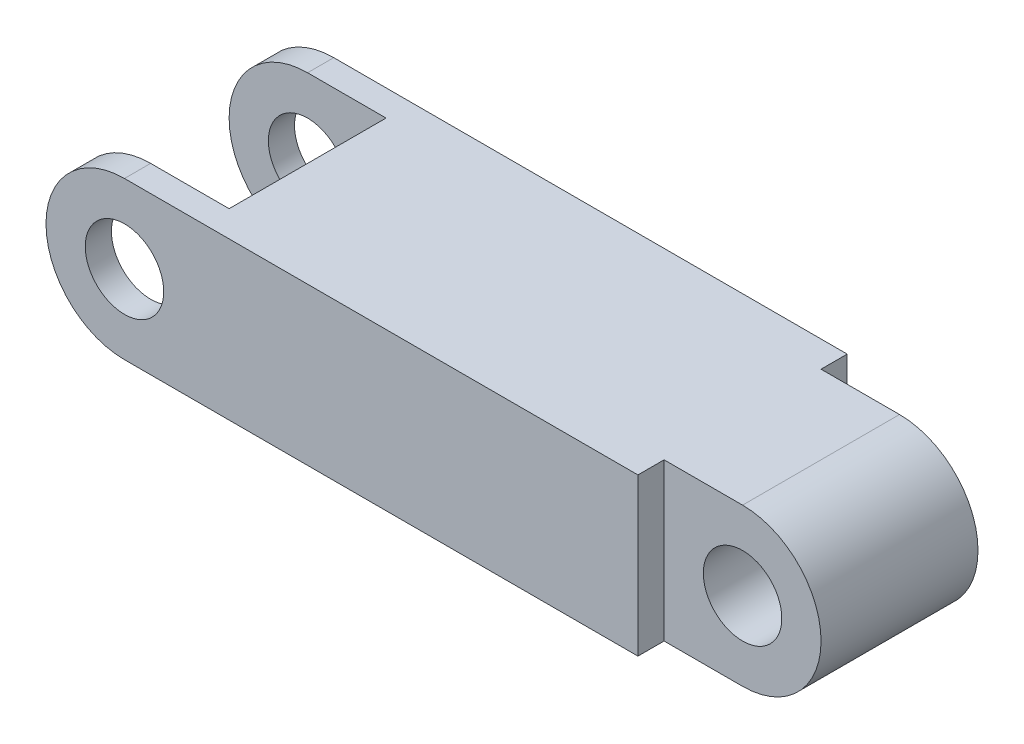
SolidWorks part; units mm, degrees
ref_plane "Front Plane" through (0, 0, 0) normal (0, 0, 1) x (1, 0, 0)
ref_plane "Top Plane" through (0, 0, 0) normal (0, 1, 0) x (1, 0, 0)
ref_plane "Right Plane" through (0, 0, 0) normal (1, 0, 0) x (0, 0, -1)
sketch "Sketch1" plane through (0, 0, 0) normal (0, 0, 1) x (1, 0, 0)
  line L0 (0, 0) -> (113.1405, 0) construction
  line L1 (0, 15) -> (113.1405, 15)
  line L2 (0, -15) -> (113.1405, -15)
  arc A0 (0, 15) -> (0, -15) centre (0, 0) ccw
  arc A1 (113.1405, -15) -> (113.1405, 15) centre (113.1405, 0) ccw
  circle A2 centre (0, 0) radius 7.5
  circle A3 centre (113.1405, 0) radius 7.5
  point P3 (56.5702, 0)
  point P12 (95.0581, 0)
  point P13 (113.1405, 0)
  dimension "D1" = 15
  dimension "D2" = 15
  dimension "D3" = 30
extrude "Boss-Extrude1" add sketch "Sketch1" along normal blind 40
sketch "Sketch2" plane through (0, 15, 0) normal (0, 1, 0) x (1, 0, 0)
  line L0 (-15, 0) -> (-15, -40) construction
  line L1 (15, -5) -> (-15, -5)
  line L2 (15, -5) -> (15, -35)
  line L3 (15, -35) -> (-15, -35)
  line L4 (-15, -5) -> (-15, -35)
  line L6 (0, -40) -> (0, 0) construction
  line L7 (128.1405, 0) -> (98.1405, 0)
  line L8 (128.1405, 0) -> (128.1405, -5)
  line L9 (128.1405, -5) -> (98.1405, -5)
  line L10 (98.1405, 0) -> (98.1405, -5)
  line L11 (128.1405, -40) -> (98.1405, -40)
  line L12 (128.1405, -40) -> (128.1405, -35)
  line L13 (128.1405, -35) -> (98.1405, -35)
  line L14 (98.1405, -40) -> (98.1405, -35)
  point P7 (-15, -20)
  point P10 (0, -20)
  dimension "D1" = 30
  dimension "D2" = 30
extrude "Cut-Extrude1" cut sketch "Sketch2" against normal through all
